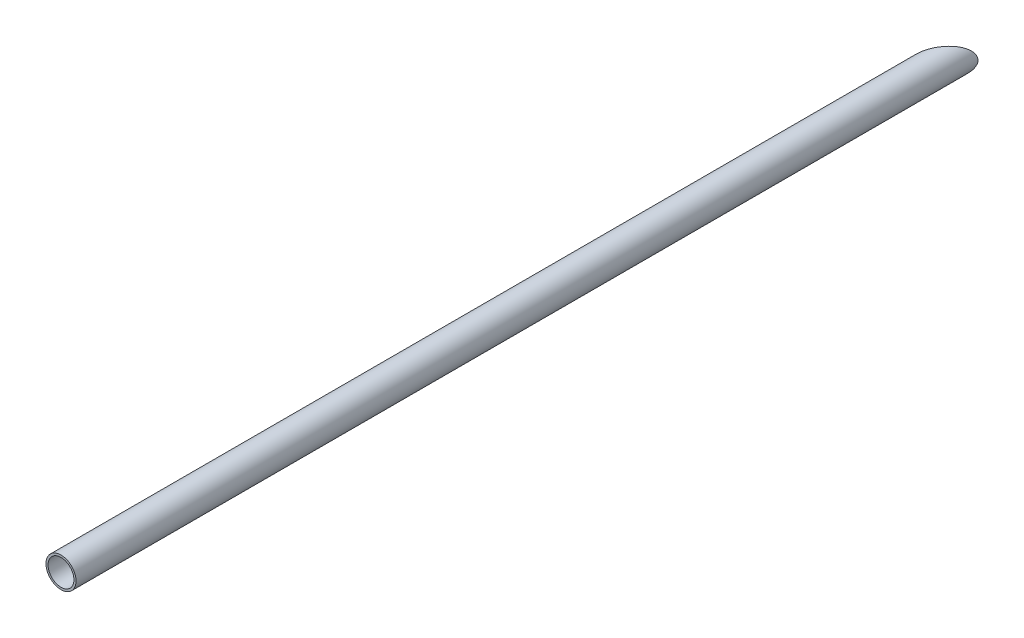
SolidWorks part; units mm, degrees
material "1060 Alloy"
ref_plane "Front Plane" through (0, 0, 0) normal (0, 0, 1) x (1, 0, 0)
ref_plane "Top Plane" through (0, 0, 0) normal (0, 1, 0) x (1, 0, 0)
ref_plane "Right Plane" through (0, 0, 0) normal (1, 0, 0) x (0, 0, -1)
sketch "Sketch1" plane through (0, 0, 0) normal (0, 0, 1) x (1, 0, 0)
  circle A0 centre (0, 0) radius 12.7
  circle A1 centre (0, 0) radius 10.922
  dimension "D1" = 25.4
  dimension "D2" = 1.778
extrude "Boss-Extrude1" add sketch "Sketch1" along normal blind 762
ref_axis "Axis1" through (0, 0, 762) along (0, 0, -1)
sketch "Sketch3" plane through (0, 0, 0) normal (0, 1, 0) x (1, 0, 0)
  line L0 (0, 0) -> (12.7, 0)
  line L1 (12.7, 0) -> (-50.8, -90.6874)
  line L2 (12.7, -762) -> (12.7, 0) construction
  line L3 (0, 0) -> (-50.8, 0)
  line L4 (-50.8, 0) -> (-50.8, -90.6874)
  line L5 (0, -762) -> (0, 0) construction
  point P3 (0, -18.1375)
  dimension "D1" = 55
  dimension "D2" = 63.5
extrude "Cut-Extrude1" cut sketch "Sketch3" against normal through all both and the other way through all
